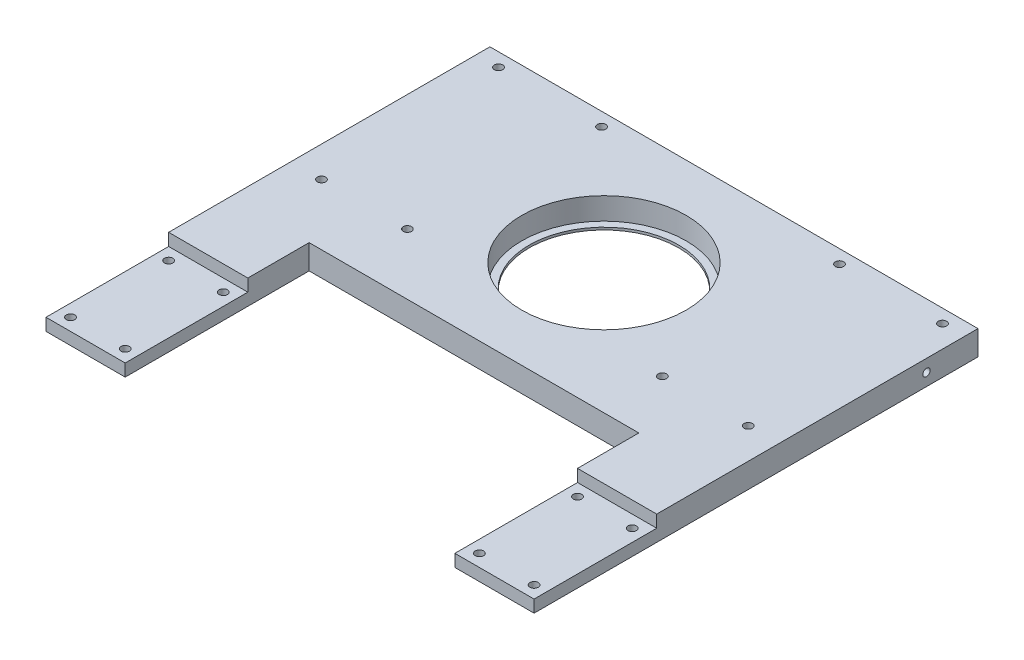
SolidWorks part; units mm, degrees
ref_plane "Ebene vorne" through (0, 0, 0) normal (0, 0, 1) x (1, 0, 0)
ref_plane "Ebene oben" through (0, 0, 0) normal (0, 1, 0) x (1, 0, 0)
ref_plane "Ebene rechts" through (0, 0, 0) normal (1, 0, 0) x (0, 0, -1)
sketch "Skizze1" plane through (0, 0, 0) normal (0, 1, 0) x (1, 0, 0)
  line L1 (-99.5, -210) -> (99.5, -210)
  line L2 (-99.5, -210) -> (-99.5, 210)
  line L3 (-99.5, 210) -> (99.5, 210)
  line L4 (99.5, -210) -> (99.5, 210)
  line L5 (-99.5, -210) -> (99.5, 210) construction
  line L6 (-99.5, 210) -> (99.5, -210) construction
  point P0 (0, 0)
  dimension "D1" = 199
  dimension "D2" = 420
extrude "Aufsatz-Linear austragen1" add sketch "Skizze1" along normal blind 10
ref_plane "Ebene1" through (0, -97.5366, 81.8429) normal (0, -0.766, 0.6428) x (1, 0, 0)
sketch "Skizze2" plane through (0, -97.5366, 81.8429) normal (0, -0.766, 0.6428) x (1, 0, 0)
  line L1 (-99.5, 167.2972) -> (99.5, 167.2972) construction
  circle A0 centre (0, 147.2972) radius 5
  dimension "D1" = 10
  dimension "D2" = 20
extrude "Schnitt-Linear austragen1" [suppressed] cut sketch "Skizze2" against normal blind 30 and the other way blind 10
sketch "Skizze3" [suppressed] plane through (0, -67.9923, 57.0523) normal (0, -0.766, 0.6428) x (1, 0, 0)
  circle A0 centre (0, 101.3345) radius 5
  dimension "D1" = 10
extrude "Aufsatz-Linear austragen2" [suppressed] add sketch "Skizze3" along normal blind 0.1
sketch "Skizze4" plane through (0, -97.5366, 81.8429) normal (0, -0.766, 0.6428) x (1, 0, 0)
  line L0 (0, 167.2972) -> (0, 159.9002) construction
  line L1 (-99.5, 167.2972) -> (99.5, 167.2972) construction
  line L2 (-25, 167.2972) -> (-25, 202.2972)
  line L3 (-25, 202.2972) -> (25, 202.2972)
  line L4 (-25, 167.2972) -> (25, 167.2972)
  line L5 (25, 167.2972) -> (25, 202.2972)
  point P10 (0, 202.2972)
  dimension "D1" = 50
  dimension "D2" = 35
extrude "Aufsatz-Linear austragen3" [suppressed] add sketch "Skizze4" against normal blind 10 separate body
sketch "Skizze5" plane through (0, 10, 0) normal (0, 1, 0) x (1, 0, 0)
  line L0 (0, 0) -> (0, -210) construction
  line L1 (-99.5, -210) -> (99.5, -210) construction
  line L2 (99.5, -210) -> (18, -210)
  line L3 (-18, -210) -> (-99.5, -56)
  line L4 (-99.5, 210) -> (-99.5, -210) construction
  line L5 (-99.5, -56) -> (-99.5, -210)
  line L6 (-99.5, -210) -> (-18, -210)
  line L7 (99.5, -56) -> (99.5, -210)
  line L8 (18, -210) -> (99.5, -56)
  line L9 (-99.5, 210) -> (-99.5, 125)
  line L10 (-99.5, 125) -> (99.5, 125)
  line L11 (99.5, -210) -> (99.5, 210) construction
  line L12 (99.5, 125) -> (99.5, 210)
  line L13 (99.5, 210) -> (-99.5, 210)
  line L14 (67.211, -56) -> (-67.211, -56)
  line L15 (-67.211, -56) -> (-2.6461, -178)
  line L16 (67.211, -56) -> (2.6461, -178)
  line L17 (-2.6461, -178) -> (2.6461, -178)
  line L18 (2.6461, -178) -> (0, -183) construction
  line L19 (-2.6461, -178) -> (0, -183) construction
  point P27 (0, -56)
  dimension "D1" = 36
  dimension "D2" = 154
  dimension "D3" = 85
  dimension "D4" = 32
  dimension "D5" = 27
extrude "Schnitt-Linear austragen2" cut sketch "Skizze5" against normal blind 10
sketch "Skizze6" plane through (0, 10, 0) normal (0, 1, 0) x (1, 0, 0)
  line L0 (0, -210) -> (0, -178) construction
  line L1 (-18, -210) -> (18, -210) construction
  line L2 (-2.6461, -178) -> (2.6461, -178) construction
  line L3 (0, -196.59) -> (-21.075, -196.59) construction
  circle A0 centre (-11, -205) radius 1.7
  circle A1 centre (-11, -188.18) radius 1.7
  circle A2 centre (11, -205) radius 1.7
  circle A3 centre (11, -188.18) radius 1.7
  dimension "D1" = 3.4
  dimension "D2" = 11
  dimension "D3" = 5
  dimension "D4" = 13.41
extrude "Schnitt-Linear austragen3" cut sketch "Skizze6" against normal through all
sketch "Skizze7" plane through (0, 0, 0) normal (0, -1, 0) x (1, 0, 0)
  line L0 (-11, 205) -> (-11, 210) construction
  line L1 (-18, 210) -> (18, 210) construction
  line L2 (-11, 205) -> (-5.1092, 205) construction
  line L3 (-11, 208.4064) -> (-8.05, 206.7032)
  line L4 (-8.05, 206.7032) -> (-8.05, 203.2968)
  line L5 (-11, 201.5936) -> (-8.05, 203.2968)
  line L6 (-11, 201.5936) -> (-13.95, 203.2968)
  line L7 (-13.95, 206.7032) -> (-13.95, 203.2968)
  line L8 (-11, 208.4064) -> (-13.95, 206.7032)
  line L9 (0, 210) -> (0, 121.6034) construction
  line L10 (11, 205) -> (11, 188.18) construction
  line L11 (11, 196.59) -> (0, 196.59) construction
  line L12 (11, 208.4064) -> (8.05, 206.7032)
  line L13 (11, 201.5936) -> (8.05, 203.2968)
  line L14 (8.05, 206.7032) -> (8.05, 203.2968)
  line L15 (11, 201.5936) -> (13.95, 203.2968)
  line L16 (13.95, 206.7032) -> (13.95, 203.2968)
  line L17 (11, 208.4064) -> (13.95, 206.7032)
  line L18 (-8.05, 186.4768) -> (-8.05, 189.8832)
  line L19 (-11, 191.5864) -> (-13.95, 189.8832)
  line L20 (-11, 191.5864) -> (-8.05, 189.8832)
  line L21 (-13.95, 186.4768) -> (-13.95, 189.8832)
  line L22 (-11, 184.7736) -> (-13.95, 186.4768)
  line L23 (-11, 184.7736) -> (-8.05, 186.4768)
  line L24 (8.05, 186.4768) -> (8.05, 189.8832)
  line L25 (11, 191.5864) -> (8.05, 189.8832)
  line L26 (11, 191.5864) -> (13.95, 189.8832)
  line L27 (13.95, 186.4768) -> (13.95, 189.8832)
  line L28 (11, 184.7736) -> (13.95, 186.4768)
  line L29 (11, 184.7736) -> (8.05, 186.4768)
  point P10 (-8.05, 205)
  dimension "D1" = 120
  dimension "D2" = 5.9
extrude "Schnitt-Linear austragen4" cut sketch "Skizze7" against normal blind 4
sketch "Skizze8" plane through (0, 10, 0) normal (0, 1, 0) x (1, 0, 0)
  line L0 (99.5, 115.41) -> (78.872, 115.41) construction
  line L1 (99.5, -56) -> (99.5, 125) construction
  line L2 (-99.5, 125) -> (99.5, 125) construction
  dimension "D1" = 9.59
ref_plane "Ebene2" through (0, 62.6966, -52.6087) normal (0, 0.766, -0.6428) x (-1, 0, 0)
sketch "Skizze9" plane through (0, 62.6966, -52.6087) normal (0, 0.766, -0.6428) x (-1, 0, 0)
  line L0 (-99.5, -81.9813) -> (-78.872, -81.9813) construction
  line L1 (-99.5, 49.3264) -> (-99.5, -89.3277) construction
  line L2 (0, -45.2589) -> (0, -16.2619) construction
  circle A0 centre (-94.5, -81.9813) radius 1.7
  circle A1 centre (94.5, -81.9813) radius 1.7
  circle A2 centre (-30, -81.9813) radius 1.7
  circle A3 centre (30, -81.9813) radius 1.7
  dimension "D1" = 3.4
  dimension "D2" = 5
  dimension "D3" = 30
extrude "Schnitt-Linear austragen5" [suppressed] cut sketch "Skizze9" against normal through all and the other way through all
ref_plane "Ebene3" through (0, 55.0361, -46.1808) normal (0, 0.766, -0.6428) x (-1, 0, 0)
sketch "Skizze10" [suppressed] plane through (0, 55.0361, -46.1808) normal (0, 0.766, -0.6428) x (-1, 0, 0)
  line L0 (-95, -81.9813) -> (-100, -81.9813) construction
  line L1 (-95, -81.9813) -> (-95, -30.0694) construction
  line L2 (-95, -78.7482) -> (-97.8, -80.3647)
  line L3 (-97.8, -80.3647) -> (-97.8, -83.5979)
  line L4 (-95, -85.2145) -> (-97.8, -83.5979)
  line L5 (-95, -85.2145) -> (-92.2, -83.5979)
  line L6 (-92.2, -80.3647) -> (-92.2, -83.5979)
  line L7 (-95, -78.7482) -> (-92.2, -80.3647)
  line L8 (0, 0) -> (0, -45.6283) construction
  line L9 (-30, -81.9813) -> (-95, -81.9813) construction
  line L10 (-62.5, -81.9813) -> (-62.5, -23.1343) construction
  line L11 (-32.8, -80.3647) -> (-32.8, -83.5979)
  line L12 (-30, -85.2145) -> (-32.8, -83.5979)
  line L13 (-30, -85.2145) -> (-27.2, -83.5979)
  line L14 (-27.2, -80.3647) -> (-27.2, -83.5979)
  line L15 (-30, -78.7482) -> (-27.2, -80.3647)
  line L16 (-30, -78.7482) -> (-32.8, -80.3647)
  line L17 (95, -78.7482) -> (92.2, -80.3647)
  line L18 (92.2, -80.3647) -> (92.2, -83.5979)
  line L19 (95, -85.2145) -> (92.2, -83.5979)
  line L20 (95, -85.2145) -> (97.8, -83.5979)
  line L21 (97.8, -80.3647) -> (97.8, -83.5979)
  line L22 (95, -78.7482) -> (97.8, -80.3647)
  line L23 (30, -78.7482) -> (32.8, -80.3647)
  line L24 (30, -78.7482) -> (27.2, -80.3647)
  line L25 (27.2, -80.3647) -> (27.2, -83.5979)
  line L26 (30, -85.2145) -> (27.2, -83.5979)
  line L27 (30, -85.2145) -> (32.8, -83.5979)
  line L28 (32.8, -80.3647) -> (32.8, -83.5979)
  point P9 (-97.8, -81.9813)
  point P31 (97.8, -81.9813)
  dimension "D1" = 120
  dimension "D2" = 5.6
extrude "Schnitt-Linear austragen6" [suppressed] cut sketch "Skizze10" against normal blind 10 and the other way blind 5
sketch "Skizze13" plane through (0, 10, 0) normal (0, 1, 0) x (1, 0, 0)
  line L0 (67.211, -56) -> (99.5, -56) construction
  line L1 (67.211, -56) -> (92.4353, -69.3492) construction
  line L2 (99.5, -56) -> (18, -210) construction
  line L3 (0, 0) -> (0, -38.1435) construction
  line L4 (2.6461, -178) -> (67.211, -56) construction
  line L5 (79.8232, -62.6746) -> (103.8351, -17.3024) construction
  line L6 (99.5, -56) -> (99.5, 125) construction
  line L7 (83.3555, -56) -> (83.3555, -1) construction
  line L8 (93.5, -58.8065) -> (101.0692, -44.504) construction
  line L9 (83.1285, -86.935) -> (57.9043, -73.5858) construction
  line L10 (71.7911, -80.935) -> (86.3039, -80.935) construction
  circle A0 centre (93.5, -58.8065) radius 1.7
  circle A1 centre (72.5142, -58.8065) radius 1.7
  circle A2 centre (81.7891, -80.935) radius 1.7
  circle A3 centre (-81.7891, -80.935) radius 1.7
  circle A4 centre (-93.5, -58.8065) radius 1.7
  circle A5 centre (-72.5142, -58.8065) radius 1.7
  dimension "D1" = 6
  dimension "D5" = 35
  dimension "D3" = 3.4
  dimension "D6" = 3.4
  dimension "D2" = 6
  dimension "D4" = 6
extrude "Schnitt-Linear austragen7" [suppressed] cut sketch "Skizze13" against normal through all
sketch "Skizze14" plane through (100.8819, 0, 53.3888) normal (0.8839, 0, 0.4678) x (0.4678, 0, -0.8839)
  line L0 (-37.9543, 5) -> (-37.9543, 10)
  line L5 (-2.9543, 0) -> (-2.9543, 10) construction
  line L6 (-37.9543, 5) -> (-2.9543, 5)
  line L7 (-2.9543, 10) -> (-177.1905, 10) construction
  line L8 (-37.9543, 10) -> (-2.9543, 10)
  line L9 (-2.9543, 10) -> (-2.9543, 5)
  dimension "D1" = 35
extrude "Schnitt-Linear austragen8" [suppressed] cut sketch "Skizze14" against normal up to surface (28.9525 mm away)
mirror "Spiegeln1" [suppressed] about plane through (0, 0, 0) normal (1, 0, 0)
sketch "Skizze15" [suppressed] plane through (95, 0, 0) normal (1, 0, 0) x (0, 0, -1)
  line L0 (4, 10) -> (4, 0)
  line L1 (4, 0) -> (65, 0)
  line L2 (65, 0) -> (65, 10)
  line L3 (65, 10) -> (4, 10)
extrude "Schnitt-Linear austragen9" [suppressed] cut sketch "Skizze15" against normal through all
sketch "Skizze16" plane through (0, 0, 0) normal (0, -1, 0) x (1, 0, 0)
  line L0 (0, 210) -> (0, 178) construction
  line L1 (-18, 210) -> (18, 210) construction
  line L2 (-2.6461, 178) -> (2.6461, 178) construction
  line L3 (11, 196.59) -> (0, 196.59) construction
  line L4 (11, 205) -> (11, 188.18) construction
  line L6 (-17.5, 193.09) -> (17.5, 193.09)
  line L7 (-17.5, 193.09) -> (-17.5, 200.09)
  line L8 (-17.5, 200.09) -> (17.5, 200.09)
  line L9 (17.5, 193.09) -> (17.5, 200.09)
  line L10 (-17.5, 193.09) -> (17.5, 200.09) construction
  line L11 (-17.5, 200.09) -> (17.5, 193.09) construction
  dimension "D1" = 7
  dimension "D2" = 35
extrude "Schnitt-Linear austragen10" cut sketch "Skizze16" against normal blind 5
sketch "Skizze17" plane through (17.5, 0, 0) normal (-1, 0, 0) x (0, 0, 1)
  line L0 (196.59, 0) -> (196.59, 11.1261) construction
  line L1 (193.09, 0) -> (200.09, 0) construction
  line L2 (193.09, 5) -> (196.59, 8.5)
  line L3 (196.59, 8.5) -> (200.09, 5)
  line L4 (200.09, 5) -> (193.09, 5)
  dimension "D1" = 90
extrude "Schnitt-Linear austragen11" cut sketch "Skizze17" along normal up to surface (35 mm away) up to face at (-17.5, 2.5, 196.59)
sketch "Skizze18" [suppressed] plane through (0, 10, 0) normal (0, 1, 0) x (1, 0, 0)
  line L0 (0, -210) -> (0, 0) construction
  line L1 (-18, -210) -> (18, -210) construction
  line L2 (62.5765, -72.2325) -> (35.4483, -67.5372)
  line L3 (15.3378, -155.8503) -> (-22.1774, -134.6566)
  line L4 (2.8247, -178) -> (62.5765, -72.2325) construction
  line L5 (-15.3378, -155.8503) -> (22.1774, -134.6566)
  line L6 (58.6594, -79.166) -> (40.7308, -76.063)
  line L7 (0, -147.1854) -> (19.5429, -147.1854) construction
  line L8 (0, -95.4) -> (31.4297, -95.4) construction
  line L9 (11.6488, -162.3803) -> (0, -155.7995)
  line L10 (-71.7468, -56) -> (-2.8247, -178) construction
  line L11 (0, -95.4) -> (-37.5153, -116.5937) construction
  line L12 (-37.5153, -116.5937) -> (-39.2566, -117.5774) construction
  line L13 (-11.6488, -162.3803) -> (0, -155.7995)
  line L14 (-58.6594, -79.166) -> (-40.7308, -76.063)
  line L15 (-62.5765, -72.2325) -> (-35.4483, -67.5372)
  circle A0 centre (0, -95.4) radius 33.5
  arc A1 (7.4594, -151.3994) -> (7.4594, -142.9713) centre (9.84, -147.1854) cw
  arc A2 (-7.4594, -151.3994) -> (-7.4594, -142.9713) centre (-9.84, -147.1854) ccw
  circle A3 centre (0, -95.4) radius 45.0879
  point P17 (0, -147.1854)
  point P36 (5, -147.1854)
  point P40 (-5, -147.1854)
  line M16 (62.5765, -72.2325) -> (2.8247, -178)
  line M18 (-2.8247, -178) -> (-71.7468, -56)
  dimension "D2" = 67
  dimension "D5" = 2
  dimension "D4" = 10
  dimension "D1" = 114.6
  dimension "D3" = 7.5
  dimension "D6" = 7.5
extrude "Aufsatz-Linear austragen4" [suppressed] add sketch "Skizze18" against normal blind 10 contours A3 L15 L14 M18 | A3 A0 M16 M18 | A3 L6 L2 M16 | A2 L5 L3 | A3 L3 L5 | L3 A1 L5 | L13 L9 L3 L5 M18 M16
sketch "Skizze19" [suppressed] plane through (0, 0, 0) normal (0, -1, 0) x (1, 0, 0)
  circle A0 centre (0, 35.4) radius 31.5
  circle A1 centre (0, 35.4) radius 33.5
  circle A2 centre (0, 35.4) radius 33.5 construction
  dimension "D1" = 63
extrude "Aufsatz-Linear austragen5" [suppressed] add sketch "Skizze19" against normal blind 1
sketch "Skizze20" plane through (0, 10, 0) normal (0, 1, 0) x (1, 0, 0)
  line L0 (99.5, 119.52) -> (55.4083, 119.52) construction
  line L1 (99.5, -56) -> (99.5, 125) construction
  line L2 (-99.5, 125) -> (99.5, 125) construction
  line L3 (0, 125) -> (0, 96.9732) construction
  line L4 (105, 43.82) -> (35.5869, 43.82) construction
  circle A0 centre (90.5, 119.52) radius 1.7
  circle A1 centre (48.5, 119.52) radius 1.7
  circle A2 centre (-48.5, 119.52) radius 1.7
  circle A3 centre (-90.5, 119.52) radius 1.7
  circle A4 centre (87, 43.82) radius 1.7
  circle A5 centre (52, 43.82) radius 1.7
  circle A6 centre (-87, 43.82) radius 1.7
  circle A7 centre (-52, 43.82) radius 1.7
  dimension "D1" = 3.4
  dimension "D2" = 5.48
  dimension "D3" = 9
  dimension "D4" = 42
  dimension "D5" = 75.7
  dimension "D6" = 12.5
  dimension "D7" = 35
extrude "Schnitt-Linear austragen12" cut sketch "Skizze20" against normal through all
sketch "Skizze21" plane through (0, 10, 0) normal (0, 1, 0) x (1, 0, 0)
  line L0 (-67.211, -56) -> (-67.211, 19)
  line L1 (-67.211, 19) -> (67.211, 19)
  line L2 (67.211, 19) -> (67.211, -56)
  line L3 (67.211, -56) -> (-67.211, -56) construction
  line L4 (-67.211, -56) -> (67.211, -56)
  dimension "D1" = 75
extrude "Schnitt-Linear austragen13" cut sketch "Skizze21" against normal through all
sketch "Skizze22" plane through (0, 10, 0) normal (0, 1, 0) x (1, 0, 0)
  line L0 (-67.211, -56) -> (-2.6461, -178)
  arc A0 (-67.211, -56) -> (-2.6461, -178) centre (60.0769, -66.7211) ccw
  line M19 (-2.6461, -178) -> (-67.211, -56)
extrude "Schnitt-Linear austragen14" cut sketch "Skizze22" against normal through all contours M19 region at (-42.1385, 10, 120.8156)
sketch "Skizze23" plane through (0, 10, 0) normal (0, 1, 0) x (1, 0, 0)
  line L0 (-18, -210) -> (-99.5, -56) construction
  line L1 (-99.5, -56) -> (-18, -210)
  arc A0 (-18, -210) -> (-99.5, -56) centre (114.4449, -41.3416) cw
  arc A2 (-67.211, -56) -> (-2.6461, -178) centre (60.0769, -66.7211) ccw construction
  dimension "D1" = 60
extrude "Aufsatz-Linear austragen6" add sketch "Skizze23" against normal blind 10
mirror "Spiegeln2" about plane through (0, 0, 0) normal (1, 0, 0) of "Aufsatz-Linear austragen6", "Schnitt-Linear austragen14"
sketch "Skizze25" plane through (0, 10, 0) normal (0, 1, 0) x (1, 0, 0)
  line L0 (-99.5, -56) -> (-67.211, -56) construction
  line L1 (-99.5, -6) -> (-99.5, -56) construction
  line L2 (-99.5, -6) -> (-67.211, -6) construction
  line L3 (-67.211, 19) -> (-67.211, -56) construction
  line L4 (-83.3555, -6) -> (-83.3555, -56) construction
  line L5 (-99.5, -31) -> (-67.211, -31) construction
  line L6 (-99.5, 125) -> (-99.5, -56) construction
  circle A0 centre (-94.5, -11) radius 1.7
  circle A1 centre (-72.211, -11) radius 1.7
  circle A2 centre (-72.211, -51) radius 1.7
  circle A3 centre (-94.5, -51) radius 1.7
  dimension "D2" = 3.4
  dimension "D1" = 50
  dimension "D3" = 5
  dimension "D4" = 5
extrude "Schnitt-Linear austragen15" cut sketch "Skizze25" against normal through all
sketch "Skizze26" plane through (-99.5, 0, 0) normal (-1, 0, 0) x (0, 0, 1)
  line L0 (6, 5) -> (6, 13.1015)
  line L1 (56, 0) -> (56, 10) construction
  line L2 (56, 5) -> (6, 5)
  line L4 (-125, 0) -> (56, 0) construction
  line L5 (56, 5) -> (56, 0)
  line L6 (6, 13.1015) -> (200.6846, 82.5463)
  line L7 (200.6846, 82.5463) -> (242.9972, -41.0376)
  line L8 (242.9972, -41.0376) -> (91.2415, -60.2848)
  line L9 (91.2415, -60.2848) -> (56, 0)
  dimension "D1" = 50
mirror "Spiegeln3" about plane through (0, 0, 0) normal (1, 0, 0) of "Schnitt-Linear austragen15"
extrude "Schnitt-Linear austragen16" cut sketch "Skizze26" against normal through all
sketch "Skizze27" plane through (0, 10, 0) normal (0, 1, 0) x (1, 0, 0)
  line L0 (0, 19) -> (0, 125) construction
  line L1 (67.211, 19) -> (-67.211, 19) construction
  line L2 (-99.5, 125) -> (99.5, 125) construction
  circle A0 centre (0, 72) radius 33.5
  dimension "D1" = 67
extrude "Schnitt-Linear austragen17" cut sketch "Skizze27" against normal through all
sketch "Skizze28" plane through (0, 0, 0) normal (0, -1, 0) x (1, 0, 0)
  circle A0 centre (0, -72) radius 30.5
  circle A1 centre (0, -72) radius 33.5 construction
  circle A2 centre (0, -72) radius 36.0063
  dimension "D1" = 3
extrude "Aufsatz-Linear austragen7" add sketch "Skizze28" against normal blind 1
sketch "Skizze29" plane through (-99.5, 0, 0) normal (-1, 0, 0) x (0, 0, 1)
  line L0 (-125, 5) -> (-93.4233, 5) construction
  line L1 (-125, 0) -> (-125, 10) construction
  circle A0 centre (-104, 5) radius 1.5
  dimension "D1" = 3
  dimension "D2" = 21
extrude "Schnitt-Linear austragen18" cut sketch "Skizze29" against normal blind 10
sketch "Skizze30" plane through (0, 0, -125) normal (0, 0, -1) x (-1, 0, 0)
  line L0 (99.5, 5) -> (60.2539, 5) construction
  line L1 (99.5, 0) -> (99.5, 10) construction
  circle A0 centre (94.5, 5) radius 1.5
  circle A1 centre (78.5, 5) radius 1.5
  dimension "D1" = 3
  dimension "D2" = 5
  dimension "D3" = 21
extrude "Schnitt-Linear austragen19" cut sketch "Skizze30" against normal blind 10
mirror "Spiegeln4" about plane through (0, 0, 0) normal (1, 0, 0) of "Schnitt-Linear austragen18", "Schnitt-Linear austragen19"
sketch "Skizze31" plane through (0, 0, 0) normal (0, -1, 0) x (1, 0, 0)
  line L0 (0, -125) -> (0, -73.0202) construction
  line L1 (-99.5, -125) -> (99.5, -125) construction
  circle A0 centre (-90.5, -119.52) radius 2.95
  circle A1 centre (-48.5, -119.52) radius 2.95
  circle A2 centre (-87, -43.82) radius 2.95
  circle A3 centre (-52, -43.82) radius 2.95
  circle A4 centre (52, -43.82) radius 2.95
  circle A5 centre (87, -43.82) radius 2.95
  circle A6 centre (48.5, -119.52) radius 2.95
  circle A7 centre (90.5, -119.52) radius 2.95
  dimension "D1" = 5.9
extrude "Schnitt-Linear austragen20" cut sketch "Skizze31" against normal blind 3.5
